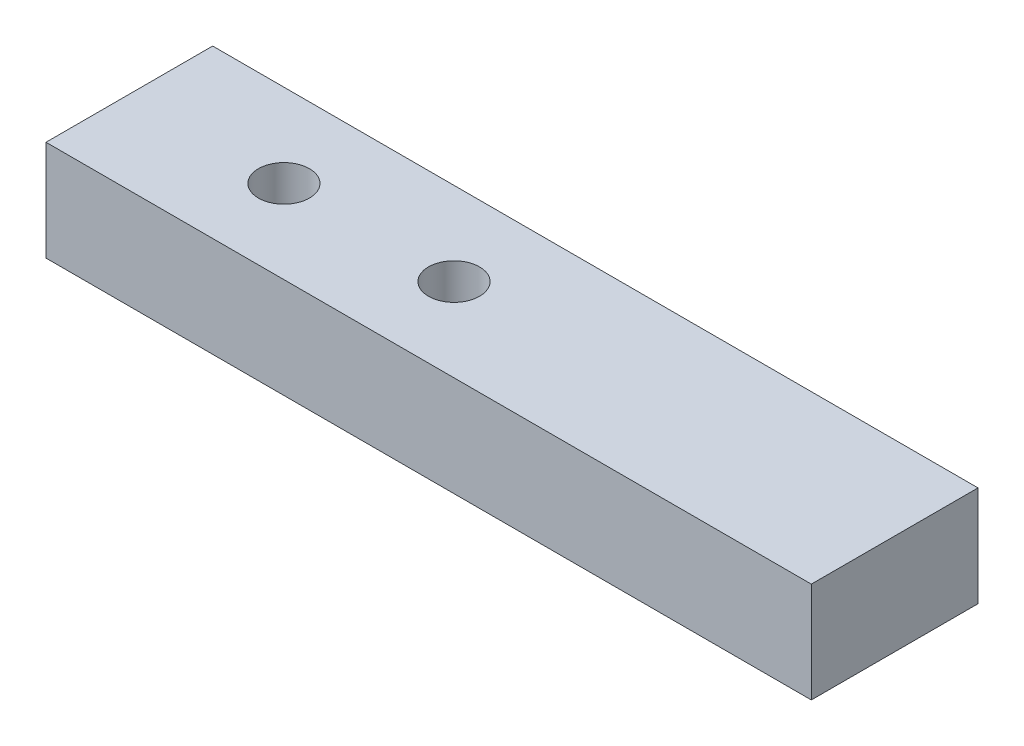
SolidWorks part; units mm, degrees
ref_plane "Front Plane" through (0, 0, 0) normal (0, 0, 1) x (1, 0, 0)
ref_plane "Top Plane" through (0, 0, 0) normal (0, 1, 0) x (1, 0, 0)
ref_plane "Right Plane" through (0, 0, 0) normal (1, 0, 0) x (0, 0, -1)
sketch "Sketch1" plane through (0, 0, 0) normal (0, 1, 0) x (1, 0, 0)
  line L1 (-22.5, -4.9) -> (22.5, -4.9)
  line L2 (-22.5, -4.9) -> (-22.5, 4.9)
  line L3 (-22.5, 4.9) -> (22.5, 4.9)
  line L4 (22.5, -4.9) -> (22.5, 4.9)
  line L5 (-22.5, -4.9) -> (22.5, 4.9) construction
  line L6 (-22.5, 4.9) -> (22.5, -4.9) construction
  circle A0 centre (-13.41, 0) radius 1.5
  circle A1 centre (-3.41, 0) radius 1.5
  point P0 (0, 0)
  point P10 (-22.5, 0)
  dimension "D3" = 3
  dimension "D1" = 9.8
  dimension "D2" = 45
  dimension "D4" = 10
  dimension "D5" = 9.09
extrude "Boss-Extrude1" add sketch "Sketch1" along normal blind 5.9
